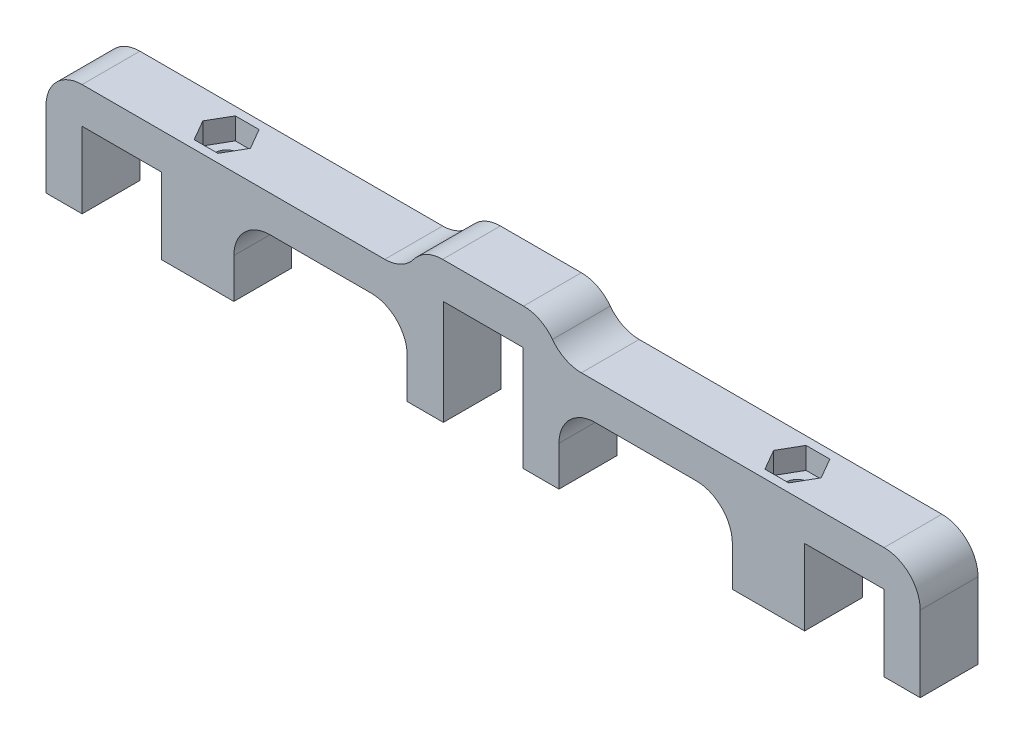
SolidWorks part; units mm, degrees
ref_plane "Plan de face" through (0, 0, 0) normal (0, 0, 1) x (1, 0, 0)
ref_plane "Plan de dessus" through (0, 0, 0) normal (0, 1, 0) x (1, 0, 0)
ref_plane "Plan de droite" through (0, 0, 0) normal (1, 0, 0) x (0, 0, -1)
sketch "Esquisse1" plane through (0, 0, 0) normal (0, 0, 1) x (1, 0, 0)
  line L0 (0, 10.5) -> (0, 15.5)
  line L1 (0, 0) -> (5, 0)
  line L2 (0, 0) -> (0, 10.5)
  line L3 (0, 10.5) -> (5, 10.5) construction
  line L4 (5, 0) -> (5, 10.5)
  line L5 (16, 0) -> (26, 0)
  line L6 (16, 0) -> (16, 10.5)
  line L7 (16, 10.5) -> (26, 10.5) construction
  line L8 (26, 0) -> (26, 10.5)
  line L9 (95, 0) -> (105, 0)
  line L10 (95, 0) -> (95, 10.5)
  line L11 (95, 10.5) -> (105, 10.5) construction
  line L12 (105, 0) -> (105, 10.5)
  line L13 (116, 0) -> (121, 0)
  line L14 (116, 0) -> (116, 10.5)
  line L15 (116, 10.5) -> (121, 10.5) construction
  line L16 (121, 0) -> (121, 10.5)
  line L17 (0, 15.5) -> (50, 15.5)
  line L18 (121, 15.5) -> (121, 10.5)
  line L19 (5, 10.5) -> (16, 10.5)
  line L20 (105, 10.5) -> (116, 10.5)
  line L21 (95, 10.5) -> (71, 10.5)
  line L22 (50, 10.5) -> (26, 10.5)
  line L24 (55, 10.5) -> (55, 14.5)
  line L25 (55, 14.5) -> (66, 14.5)
  line L26 (66, 10.5) -> (66, 14.5)
  line L27 (71, 15.5) -> (121, 15.5)
  line L29 (50, 15.5) -> (50, 19.5)
  line L30 (50, 19.5) -> (71, 19.5)
  line L31 (71, 15.5) -> (71, 19.5)
  line L32 (50, 10.5) -> (55, 10.5) construction
  line L34 (55, 10.5) -> (55, 0)
  line L35 (55, 0) -> (50, 0)
  line L36 (50, 10.5) -> (50, 0)
  line L38 (66, 10.5) -> (66, 0)
  line L39 (66, 0) -> (71, 0)
  line L40 (71, 10.5) -> (71, 0)
  line L41 (66, 10.5) -> (71, 10.5) construction
  dimension "D1" = 11
  dimension "D2" = 121
  dimension "D3" = 5
  dimension "D4" = 5
  dimension "D5" = 10.5
  dimension "D6" = 4
  dimension "D7" = 5
  dimension "D8" = 5
  dimension "D9" = 4
  dimension "D10" = 10
extrude "Boss.-Extru.1" add sketch "Esquisse1" along normal blind 8
sketch "Esquisse2" plane through (0, 15.5, 0) normal (0, 1, 0) x (1, 0, 0)
  line L1 (21, 0) -> (21, -8) construction
  line L2 (50, 0) -> (0, 0) construction
  line L3 (50, -8) -> (0, -8) construction
  line L4 (0, -8) -> (0, 0) construction
  line L5 (60.5, 0) -> (60.5, -8) construction
  line L6 (71, 0) -> (50, 0) construction
  line L7 (71, -8) -> (50, -8) construction
  circle A0 centre (21, -4) radius 1.65
  circle A1 centre (100, -4) radius 1.65
  point P10 (21, -4)
  dimension "D2" = 3.3
  dimension "D1" = 21
extrude "Enlèv. mat.-Extru.1" cut sketch "Esquisse2" against normal up to next
fillet "Congé1" radius 5 2 edges at (50, 19.5, 4) (71, 19.5, 4)
sketch "Esquisse3" plane through (0, 15.5, 0) normal (0, 1, 0) x (1, 0, 0)
  line L6 (19.3546, -1.15) -> (22.6454, -1.15)
  line L7 (22.6454, -1.15) -> (24.2909, -4)
  line L8 (24.2909, -4) -> (22.6454, -6.85)
  line L9 (22.6454, -6.85) -> (19.3546, -6.85)
  line L10 (19.3546, -6.85) -> (17.7091, -4)
  line L11 (17.7091, -4) -> (19.3546, -1.15)
  line L12 (19.3546, -1.15) -> (22.6454, -6.85) construction
  line L13 (60.5, 0) -> (60.5, -8) construction
  line L14 (66.101, 0) -> (54.899, 0) construction
  line L15 (66.101, -8) -> (54.899, -8) construction
  line L16 (101.6454, -1.15) -> (98.3546, -6.85) construction
  line L17 (103.2909, -4) -> (101.6454, -1.15)
  line L18 (101.6454, -6.85) -> (103.2909, -4)
  line L19 (98.3546, -6.85) -> (101.6454, -6.85)
  line L20 (96.7091, -4) -> (98.3546, -6.85)
  line L21 (98.3546, -1.15) -> (96.7091, -4)
  line L22 (101.6454, -1.15) -> (98.3546, -1.15)
  point P2 (21, -6.85)
  point P7 (21, -4)
  point P8 (21, -4)
  point P22 (100, -4)
  dimension "D1" = 5.7
  dimension "D2" = 5.7
  dimension "D3" = 120
extrude "Enlèv. mat.-Extru.2" cut sketch "Esquisse3" against normal blind 3
fillet "Congé2" radius 5 2 edges at (121, 15.5, 4) (0, 15.5, 4)
fillet "Congé3" radius 5 4 edges at (50, 10.5, 4) (95, 10.5, 4) (71, 10.5, 4) (26, 10.5, 4)
fillet "Congé4" radius 5 2 edges at (71, 15.5, 4) (50, 15.5, 4)
